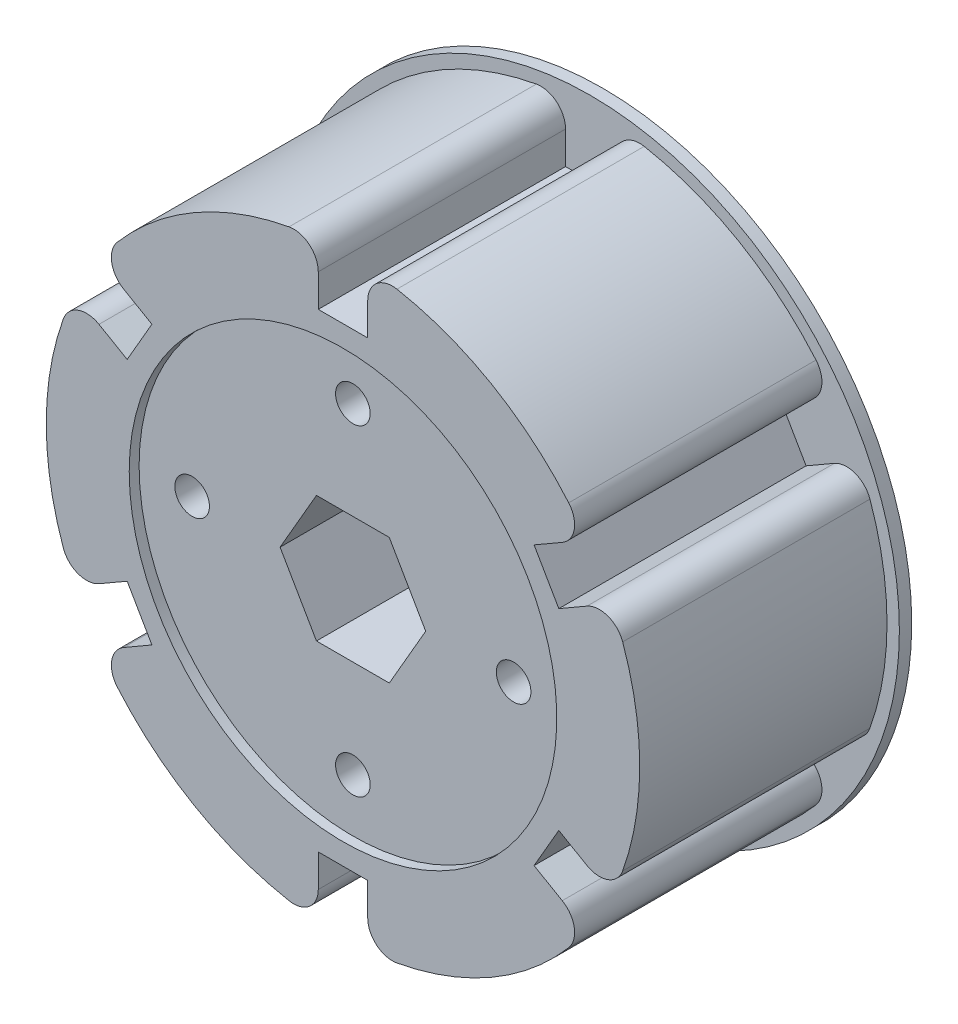
SolidWorks part; units mm, degrees
ref_plane "Front Plane" through (0, 0, 0) normal (0, 0, 1) x (1, 0, 0)
ref_plane "Top Plane" through (0, 0, 0) normal (0, 1, 0) x (1, 0, 0)
ref_plane "Right Plane" through (0, 0, 0) normal (1, 0, 0) x (0, 0, -1)
sketch "Sketch1" plane through (0, 0, 0) normal (0, 0, 1) x (1, 0, 0)
  circle A0 centre (0, 0) radius 30.48
  dimension "D1" = 60.96
extrude "Boss-Extrude1" add sketch "Sketch1" along normal mid plane 25.4
sketch "Sketch2" plane through (0, 0, -12.7) normal (0, 0, 1) x (1, 0, 0)
  circle A0 centre (0, 0) radius 31.75
  dimension "D1" = 63.5
extrude "Boss-Extrude2" add sketch "Sketch2" against normal blind 1.27
sketch "Sketch3" plane through (0, 0, -12.7) normal (0, 0, 1) x (1, 0, 0)
  line L0 (0, 30.48) -> (0, -31.75) construction
  line L1 (-2.54, 31.75) -> (-2.54, 24.13)
  line L2 (2.54, 31.75) -> (2.54, 24.13)
  line L3 (-2.54, 24.13) -> (2.54, 24.13)
  line L4 (-2.54, 31.75) -> (2.54, 31.75)
  circle A1 centre (0, 0) radius 30.48 construction
  circle A2 centre (0, 0) radius 31.75 construction
  dimension "D2" = 6.35
  dimension "D1" = 2.54
  dimension "D3" = 7.62
extrude "Cut-Extrude1" cut sketch "Sketch3" along normal through all
fillet "Fillet1" radius 2.54 2 edges at (2.54, 30.374, 0) (-2.54, 30.374, 0)
ref_axis "Axis2" through (0, 0, 20.0025) along (0, 0, -1)
pattern_circular "CirPattern1" count 6 over 360 about axis through (0, 0, 20.0025) along (0, 0, -1) of "Cut-Extrude1", "Fillet1"
sketch "Sketch6" plane through (0, 0, -13.97) normal (0, 0, -1) x (-1, 0, 0)
  line L0 (-3.7395, 6.477) -> (3.7395, 6.477)
  line L1 (3.7395, 6.477) -> (7.479, 0)
  line L2 (7.479, 0) -> (3.7395, -6.477)
  line L3 (3.7395, -6.477) -> (-3.7395, -6.477)
  line L4 (-3.7395, -6.477) -> (-7.479, 0)
  line L5 (-7.479, 0) -> (-3.7395, 6.477)
  circle A0 centre (0, 0) radius 6.477
  point P6 (0, 6.477)
  point P18 (0, 0)
  dimension "D1" = 12.954
  dimension "D3" = 12.954
  dimension "D2" = 6
extrude "Cut-Extrude4" cut sketch "Sketch6" against normal through all both and the other way through all contours A0 | A0 L5 L4 | A0 L4 L3 | A0 L3 L2 | A0 L2 L1 | A0 L1 L0 | A0 L0 L5 region at (3.3472, 5.7975, -13.97) region at (-3.3472, 5.7975, -13.97) region at (0, 0, -13.97) region at (6.6944, 0, -13.97) region at (-6.6944, 0, -13.97) region at (3.3472, -5.7975, -13.97) region at (-3.3472, -5.7975, -13.97)
sketch "Sketch7" plane through (0, 0, -13.97) normal (0, 0, -1) x (-1, 0, 0)
  line L0 (0, 0) -> (-16.51, 0) construction
  circle A0 centre (-16.51, 0) radius 1.778
  circle A1 centre (0, 16.51) radius 1.778
  circle A2 centre (16.51, 0) radius 1.778
  circle A3 centre (0, -16.51) radius 1.778
  point P13 (0, 0)
  dimension "D2" = 3.556
  dimension "D1" = 16.51
  dimension "D3" = 4
extrude "Cut-Extrude5" cut sketch "Sketch7" against normal through all both
sketch "Sketch8" plane through (0, 0, 12.7) normal (0, 0, -1) x (-1, 0, 0)
  circle A0 centre (0, 0) radius 21.9589
  dimension "D1" = 43.9178
extrude "Cut-Extrude6" cut sketch "Sketch8" along normal blind 1.016
